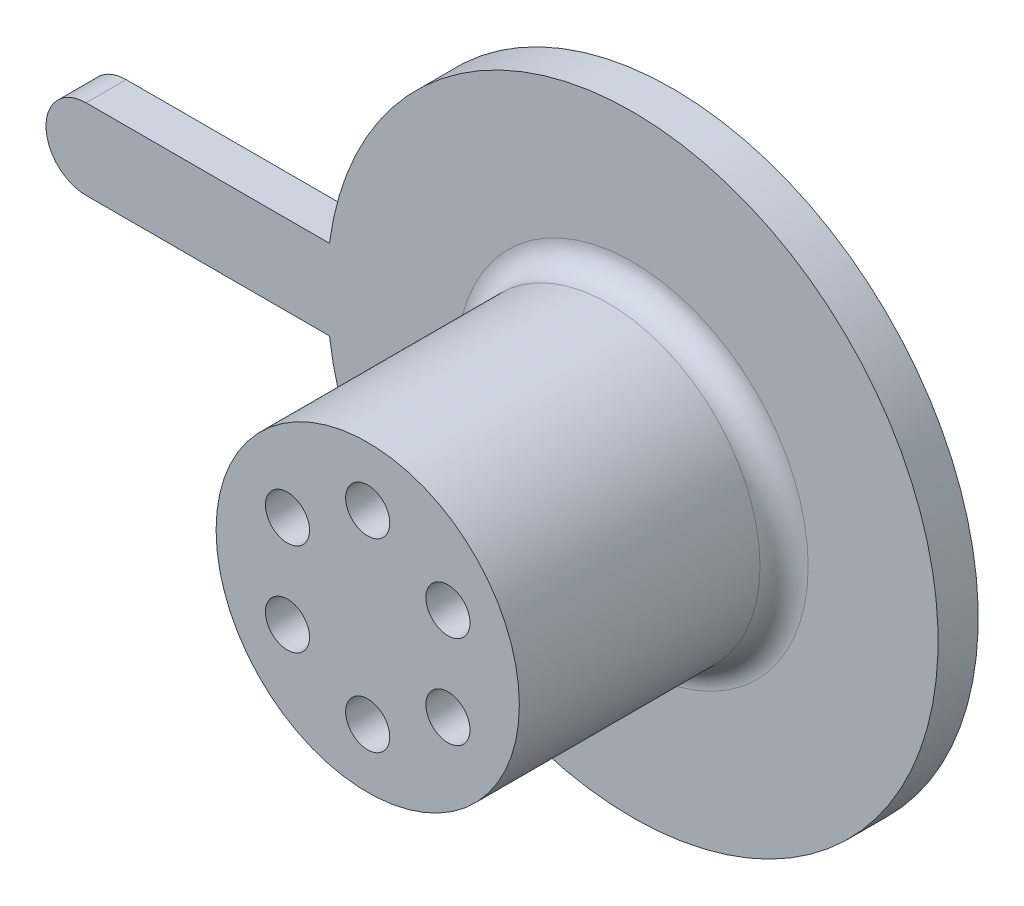
SolidWorks part; units mm, degrees
ref_plane "Front Plane" through (0, 0, 0) normal (0, 0, 1) x (1, 0, 0)
ref_plane "Top Plane" through (0, 0, 0) normal (0, 1, 0) x (1, 0, 0)
ref_plane "Right Plane" through (0, 0, 0) normal (1, 0, 0) x (0, 0, -1)
sketch "Sketch4" plane through (0, 0, 0) normal (0, 0, 1) x (1, 0, 0)
  line L0 (-38.1, 0) -> (-68.1, 0)
  line L1 (-68.1, 0) -> (-68.1, 5)
  line L2 (-68.1, 0) -> (-68.1, -5)
  line L3 (-68.1, 5) -> (-37.7705, 5)
  line L4 (-68.1, -5) -> (-37.7705, -5)
  circle A0 centre (0, 0) radius 38.1
  arc A1 (-68.1, 5) -> (-68.1, -5) centre (-68.1, 0) ccw
  dimension "D1" = 30
  dimension "D2" = 76.2
extrude "Boss-Extrude3" add sketch "Sketch4" along normal blind 5 contours A0 | A0 L3 L1 L0 | A0 L0 L2 L4 | L1 A1 L2 region at (-53.045, -2.5046, 0) region at (-53.045, 2.5046, 0) region at (0, 0, 0) region at (-70.2221, 0, 0)
sketch "Sketch5" plane through (0, 0, 5) normal (0, 0, 1) x (1, 0, 0)
  circle A0 centre (0, 0) radius 18.9
extrude "Boss-Extrude4" add sketch "Sketch5" along normal blind 33
fillet "Fillet4" radius 3 1 edges at (18.9, 0, 5)
sketch "Sketch6" plane through (0, 0, 38) normal (0, 0, 1) x (1, 0, 0)
  line L1 (0, 11.547) -> (-10, 5.7735)
  line L2 (-10, 5.7735) -> (-10, -5.7735)
  line L3 (-10, -5.7735) -> (0, -11.547)
  line L4 (0, -11.547) -> (10, -5.7735)
  line L5 (10, -5.7735) -> (10, 5.7735)
  line L6 (10, 5.7735) -> (0, 11.547)
  circle A0 centre (0, 0) radius 10 construction
  circle A1 centre (0, 11.547) radius 2.75
  circle A2 centre (10, 5.7735) radius 2.75
  circle A3 centre (10, -5.7735) radius 2.75
  circle A4 centre (0, -11.547) radius 2.75
  circle A5 centre (-10, -5.7735) radius 2.75
  circle A6 centre (-10, 5.7735) radius 2.75
extrude "Cut-Extrude4" cut sketch "Sketch6" against normal blind 39.48 contours L6 A1 L1 | L1 A1 L6 | L5 A2 L6 | L6 A2 L5 | L4 A3 L5 | L5 A3 L4 | L1 A6 L2 | L2 A6 L1 | L3 A5 L2 | L2 A5 L3 | L3 A4 L4 | L4 A4 L3 region at (0, 10.0309, 38) region at (0, 12.3051, 38) region at (-8.687, 5.0154, 38) region at (-10.6565, 6.1525, 38) region at (10.6565, 6.1525, 38) region at (8.687, 5.0154, 38) region at (-8.687, -5.0154, 38) region at (-10.6565, -6.1525, 38) region at (10.6565, -6.1525, 38) region at (8.687, -5.0154, 38) region at (0, -10.0309, 38) region at (0, -12.3051, 38)
